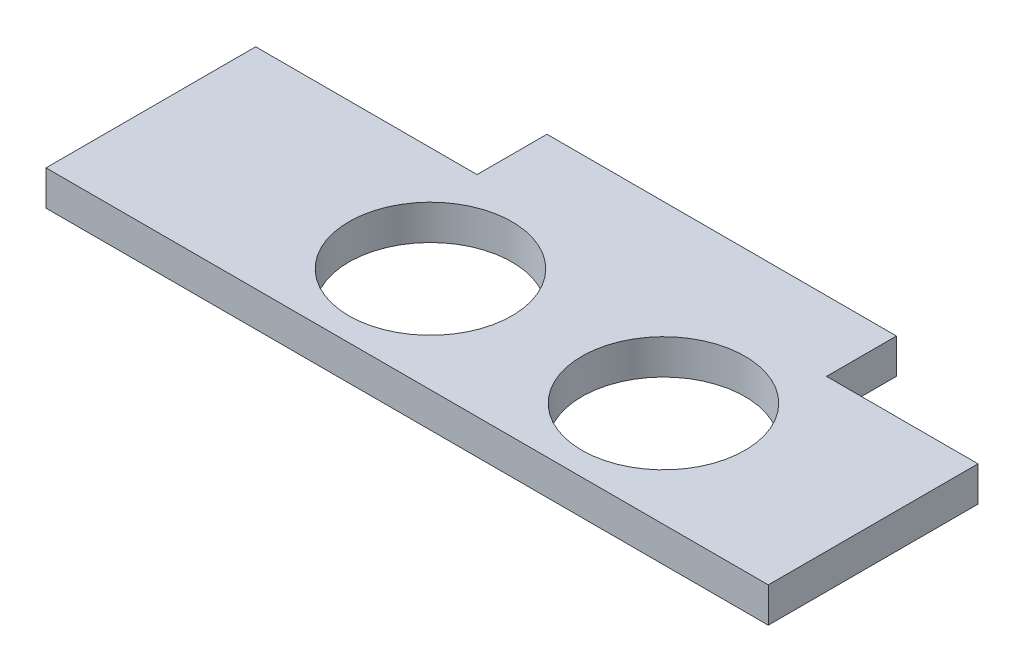
SolidWorks part; units mm, degrees
ref_plane "Front Plane" through (0, 0, 0) normal (0, 0, 1) x (1, 0, 0)
ref_plane "Top Plane" through (0, 0, 0) normal (0, 1, 0) x (1, 0, 0)
ref_plane "Right Plane" through (0, 0, 0) normal (1, 0, 0) x (0, 0, -1)
sketch "Sketch1" plane through (0, 0, 0) normal (0, 1, 0) x (1, 0, 0)
  line L0 (-3, 0) -> (-3, 50000) construction
  line L1 (3, 0) -> (3, 50000) construction
  line L2 (5, 0) -> (5, 50000) construction
  line L3 (-30.5, 9) -> (5.5, 9)
  line L4 (-30.5, 9) -> (-30.5, -9)
  line L5 (-30.5, -9) -> (5.5, -9)
  line L6 (5.5, 9) -> (5.5, -9) construction
  line L7 (-5, 0) -> (-5, 50000) construction
  line L9 (25.5, 9) -> (-10.5, 9)
  line L10 (25.5, 9) -> (25.5, -9)
  line L11 (25.5, -9) -> (-10.5, -9)
  line L12 (-10.5, 9) -> (-10.5, -9) construction
  line L13 (-30.5, 9) -> (25.5, 9)
  line L14 (-30.5, 9) -> (-30.5, -9)
  line L15 (-30.5, -9) -> (25.5, -9)
  line L16 (25.5, 9) -> (25.5, -9)
  circle A0 centre (0, 0) radius 3 construction
  circle A1 centre (-12.5, 0) radius 7
  circle A2 centre (7.5, 0) radius 7
  circle A3 centre (-10, 0) radius 15 construction
  circle A4 centre (10, 0) radius 15 construction
  point P11 (-30.5, 0)
  point P18 (-12.5, 9)
  point P25 (9.3539, 9)
  point P26 (7.5, 9)
  point P28 (25.5, 0)
  dimension "D1" = 6
  dimension "D2" = 36
  dimension "D5" = 14
  dimension "D6" = 14
  dimension "D9" = 2
  dimension "D7" = 2
  dimension "D8" = 7
  dimension "D10" = 12.5
  dimension "D3" = 7
  dimension "D4" = 18
  dimension "D11" = 7.5
  dimension "D12" = 36
extrude "Boss-Extrude2" add sketch "Sketch1" along normal blind 3 contours A2 | L14 L13 L16 L15 | A1 region at (7.5, 0, 0)
sketch "Sketch2" plane through (0, 0, 0) normal (0, -1, 0) x (1, 0, 0)
  line L0 (-30.5, -9) -> (25.5, -9) construction
  line L1 (-30.5, -9) -> (-36.5, -9)
  line L2 (-30.5, -9) -> (-30.5, 9)
  line L3 (-30.5, 9) -> (-36.5, 9)
  line L4 (-36.5, -9) -> (-36.5, 9)
  line L5 (-17.5, -9) -> (12.5, -9)
  line L6 (-17.5, -9) -> (-17.5, -15)
  line L7 (-17.5, -15) -> (12.5, -15)
  line L8 (12.5, -9) -> (12.5, -15)
  line L9 (-30.5, -9) -> (-17.5, -9) construction
  line L10 (12.5, -9) -> (25.5, -9) construction
  point P13 (-15.0851, -9)
  dimension "D1" = 6
  dimension "D2" = 6
  dimension "D3" = 30
extrude "Boss-Extrude3" add sketch "Sketch2" against normal up to surface (3 mm away) up to face at (-2.5, 3, 0)
